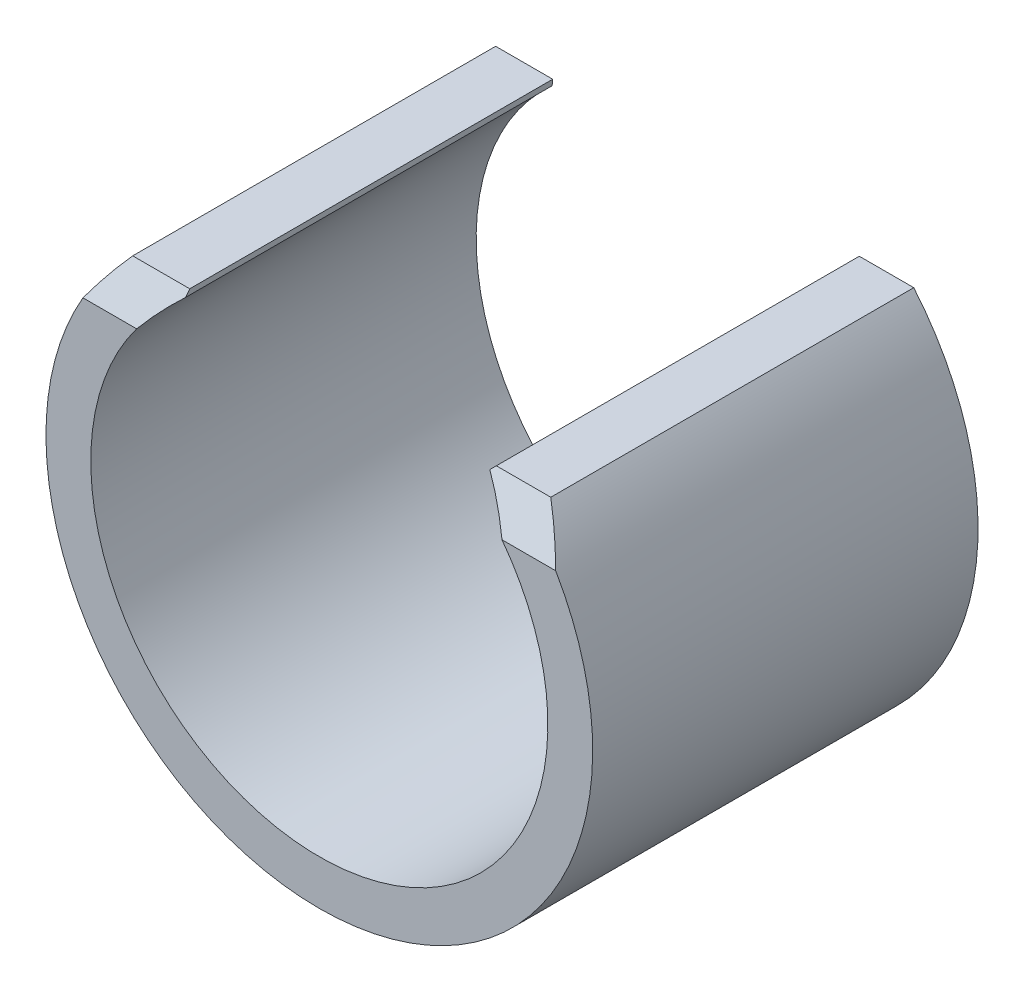
SolidWorks part; units mm, degrees
material "PLA"
ref_plane "前视基准面" through (0, 0, 0) normal (0, 0, 1) x (1, 0, 0)
ref_plane "上视基准面" through (0, 0, 0) normal (0, 1, 0) x (1, 0, 0)
ref_plane "右视基准面" through (0, 0, 0) normal (1, 0, 0) x (0, 0, -1)
sketch "草图1" plane through (0, 0, 0) normal (0, 0, 1) x (1, 0, 0)
  line L2 (-135.3404, -116.6597) -> (-128.8404, -116.6597) construction
  line L3 (-128.8404, -116.6597) -> (-127.4253, -116.6597)
  line L5 (-135.3404, -116.6597) -> (-136.7554, -116.6597)
  arc A0 (-135.3404, -116.6597) -> (-128.8404, -116.6597) centre (-132.0904, -120.59) ccw
  arc A1 (-136.7554, -116.6597) -> (-127.4253, -116.6597) centre (-132.0904, -120.59) ccw
  circle A2 centre (-132.0904, -120.59) radius 6.1 construction
  circle A3 centre (-132.0904, -120.59) radius 5.1 construction
  dimension "D1" = 10.2
  dimension "D3" = 6.5
  dimension "D2" = 1
extrude "凸台-拉伸1" add sketch "草图1" along normal blind 8.6
chamfer "倒角1" distance 0.5 angle 60 2 edges at (-128.1328, -116.6597, 8.6) (-136.0479, -116.6597, 8.6) first distance on face at (-128.1328, -116.6597, 4.3) first distance on face at (-136.0479, -116.6597, 4.3)
chamfer "倒角2" distance 0.2 angle 45 2 edges at (-135.3404, -116.6597, 4.05) (-128.8404, -116.6597, 4.05) first distance on face at (-132.0904, -119.806, 5.562) first distance on face at (-128.1328, -116.6597, 4.05)
